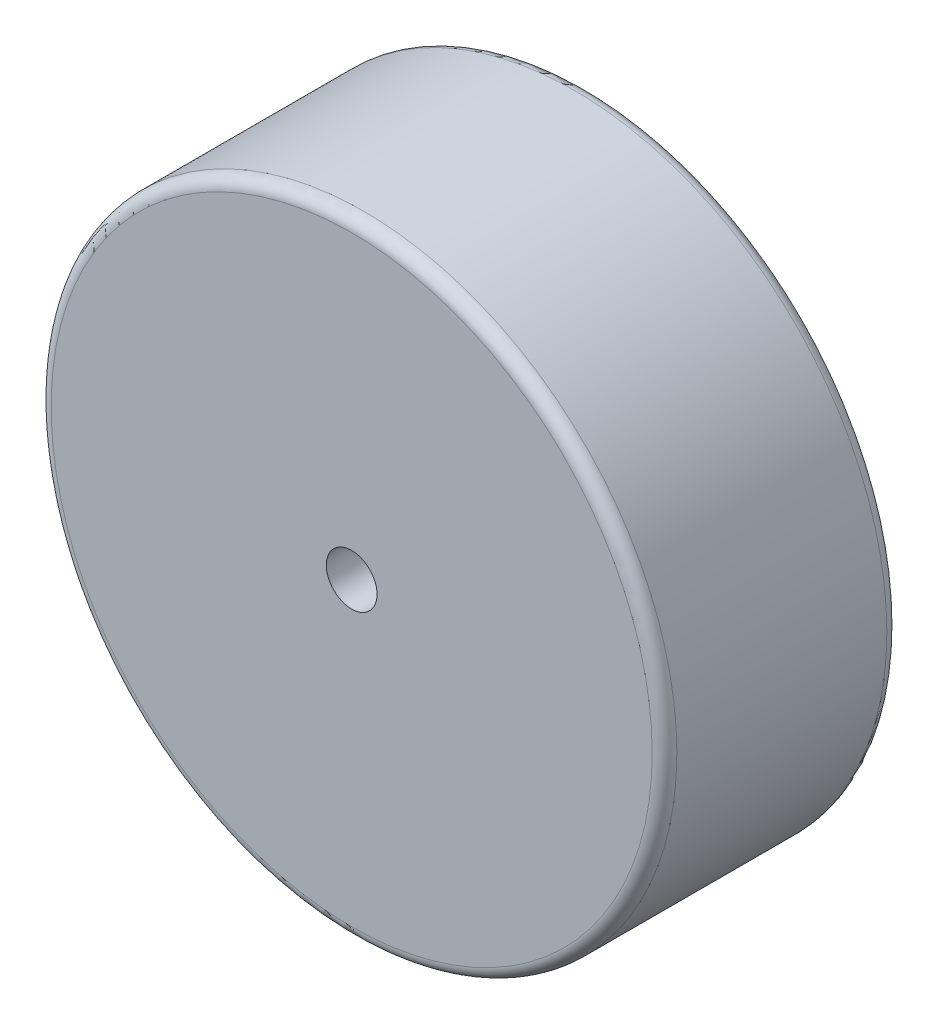
SolidWorks part; units mm, degrees
ref_plane "Front Plane" through (0, 0, 0) normal (0, 0, 1) x (1, 0, 0)
ref_plane "Top Plane" through (0, 0, 0) normal (0, 1, 0) x (1, 0, 0)
ref_plane "Right Plane" through (0, 0, 0) normal (1, 0, 0) x (0, 0, -1)
sketch "body sketch" plane through (0, 0, 0) normal (0, 0, 1) x (1, 0, 0)
  circle A0 centre (0, 0) radius 25.4
  dimension "D1" = 50.8
extrude "wheel body" add sketch "body sketch" along normal mid plane 19.05 contours A0
sketch "hole sketch" plane through (0, 0, 9.525) normal (0, 0, 1) x (1, 0, 0)
  circle A0 centre (0, 0) radius 2.06
  dimension "D1" = 4.12
fillet "fillet wheel" radius 1 2 edges at (25.4, 0, -9.525) (25.4, 0, 9.525)
extrude "hole shaft" cut sketch "hole sketch" against normal up to surface (19.05 mm away) contours A0 up to face at (24.4, 0, -9.525)
